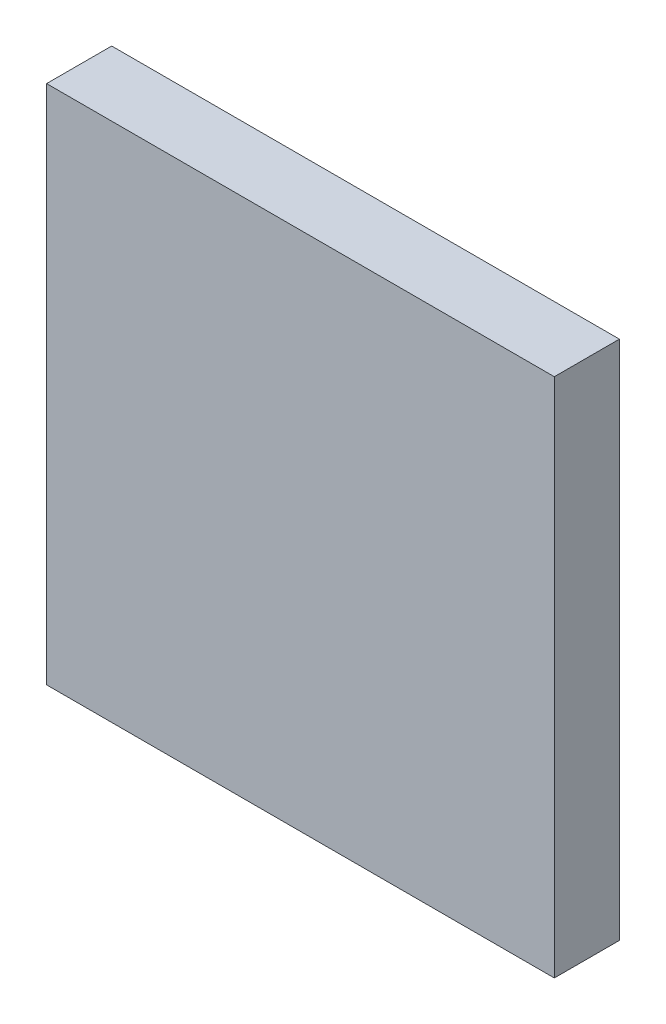
SolidWorks part; units mm, degrees
ref_plane "Ön Düzlem" through (0, 0, 0) normal (0, 0, 1) x (1, 0, 0)
ref_plane "Üst Düzlem" through (0, 0, 0) normal (0, 1, 0) x (1, 0, 0)
ref_plane "Sağ Düzlem" through (0, 0, 0) normal (1, 0, 0) x (0, 0, -1)
sketch "Çizim1" plane through (0, 0, 0) normal (0, 0, 1) x (1, 0, 0)
  line L1 (0, 0) -> (390, 0)
  line L2 (0, 0) -> (0, -400)
  line L3 (0, -400) -> (390, -400)
  line L4 (390, 0) -> (390, -400)
  dimension "D1" = 390
  dimension "D2" = 400
base flange "Taban-Flanş1" sketch "Çizim1" thickness 50 reverse thickness direction no parameters "D1"=4
sketch "Büküm-Çizgileri1" [suppressed] plane through (0, 0, 0) normal (0, 1, 0) x (1, 0, 0)
sketch "Sınırlandırma-Kutusu1" [suppressed] plane through (0, 0, 0) normal (0, 1, 0) x (1, 0, 0)
sheet metal parameters "Sac-Levha1" thickness 50 parameters "D1"=4
flat pattern "Düz-Çoğaltma1" [suppressed]
sketch "Büküm-Çizgileri2" plane through (0, 0, 0) normal (0, 1, 0) x (1, 0, 0)
sketch3d "Sınırlandırma-Kutusu2" [suppressed]
  line L0 (390, 0, 0) -> (390, -400, 0) construction
  line L1 (0, 0, 0) -> (0, -400, 0) construction
  line L2 (390, 0, 0) -> (0, 0, 0) construction
  line L3 (390, -400, 0) -> (0, -400, 0) construction
